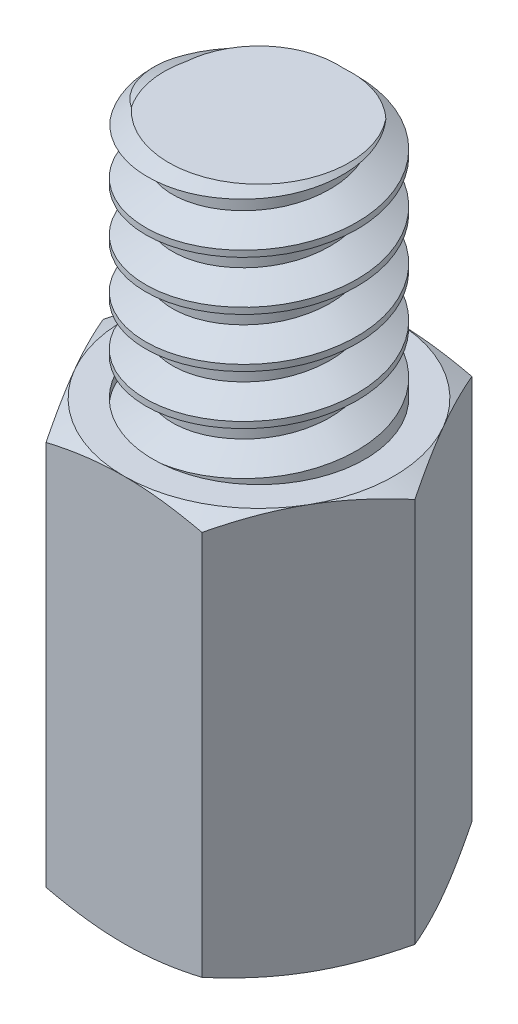
SolidWorks part; units mm, degrees
material "Brass"
ref_plane "Front Plane" through (0, 0, 0) normal (0, 0, 1) x (1, 0, 0)
ref_plane "Top Plane" through (0, 0, 0) normal (0, 1, 0) x (1, 0, 0)
ref_plane "Right Plane" through (0, 0, 0) normal (1, 0, 0) x (0, 0, -1)
sketch "Sketch23" plane through (0, 0, 0) normal (0, 1, 0) x (1, 0, 0)
  line L1 (2.5027, 0) -> (1.2513, 2.1674)
  line L2 (1.2513, 2.1674) -> (-1.2513, 2.1674)
  line L3 (-1.2513, 2.1674) -> (-2.5027, 0)
  line L4 (-2.5027, 0) -> (-1.2513, -2.1674)
  line L5 (-1.2513, -2.1674) -> (1.2513, -2.1674)
  line L6 (1.2513, -2.1674) -> (2.5027, 0)
  circle A0 centre (0, 0) radius 2.1674 construction
extrude "Boss-Extrude1" add sketch "Sketch23" along normal blind 6.5 contours L3 L4 L5 L6 L1 L2
sketch "Sketch27" plane through (0, 6.5, 0) normal (0, 1, 0) x (1, 0, 0)
  circle A0 centre (0, 0) radius 2.1674
extrude "Cut-Extrude16" cut sketch "Sketch27" against normal blind 0.25 draft 65 flip side to cut
sketch "Sketch28" plane through (0, 0, 0) normal (0, -1, 0) x (-1, 0, 0)
  circle A0 centre (0, 0) radius 2.1674
extrude "Cut-Extrude17" cut sketch "Sketch28" against normal blind 0.25 draft 65 flip side to cut
sketch "Sketch29" plane through (0, 0, 0) normal (0, -1, 0) x (-1, 0, 0)
  circle A0 centre (0, 0) radius 1.5024
extrude "Cut-Extrude18" cut sketch "Sketch29" against normal blind 4.75 contours A0
chamfer "Chamfer1" distance 0.25 distance2 0.25 1 edges at (0, 0, -1.5024)
thread "Thread1" pitch 0.5 start angle 0, offset 1.5, length 0, pitch 0.5, diameter 3.0047
ref_plane "Plane1" through (1.5024, -1.25, 0) normal (0, 0, 1) x (1, 0, 0)
sketch "Thread Profile1" plane through (1.5024, -1.25, 0) normal (0, 0, 1) x (1, 0, 0)
  line L0 (0, 0) -> (0, 0.5) construction
  line L1 (0, 0) -> (0.2706, 0.1562)
  line L2 (0.2706, 0.1562) -> (0.2706, 0.2187)
  line L3 (0.2706, 0.2187) -> (0, 0.375)
  line L4 (0.2706, 0.1875) -> (0, 0.1875) construction
  line L11 (0, 0) -> (0, 0.375)
  point P2 (0, 0)
  dimension "Pitch" = 0.5
  dimension "Profile_Angle" = 60
  dimension "Profile_Land" = 0.0625
  dimension "Profile_Height" = 0.2706
sketch "Sketch34" plane through (0, 6.5, 0) normal (0, 1, 0) x (1, 0, 0)
  circle A0 centre (0, 0) radius 1.7
extrude "Boss-Extrude2" add sketch "Sketch34" along normal blind 4 contours A0
chamfer "Chamfer2" distance 0.25 angle 45 1 edges at (0, 10.5, 1.7)
thread "Thread2" pitch 0.7937 start angle 0, offset 1.5, length 0, pitch 0.7937, diameter 3.4
ref_plane "Plane2" through (-1.7, 11.75, 0) normal (0, 0, 1) x (-1, 0, 0)
sketch "Thread Profile2" plane through (-1.7, 11.75, 0) normal (0, 0, 1) x (-1, 0, 0)
  line L0 (0, 0) -> (0, 0.7937) construction
  line L11 (0, 0) -> (0, 0.6945)
  line L12 (0, 0.6945) -> (-0.4296, 0.4465)
  line L13 (-0.4296, 0.4465) -> (-0.4296, 0.248)
  line L15 (-0.4296, 0.248) -> (0, 0)
  line L17 (-0.4296, 0.3473) -> (0, 0.3473) construction
  point P2 (0, 0)
  dimension "Pitch" = 0.7937
  dimension "Profile_Angle" = 60
  dimension "Profile_Land" = 0.1984
  dimension "Profile_Height" = 0.4296
equation "\".25.00mm\"=10"
